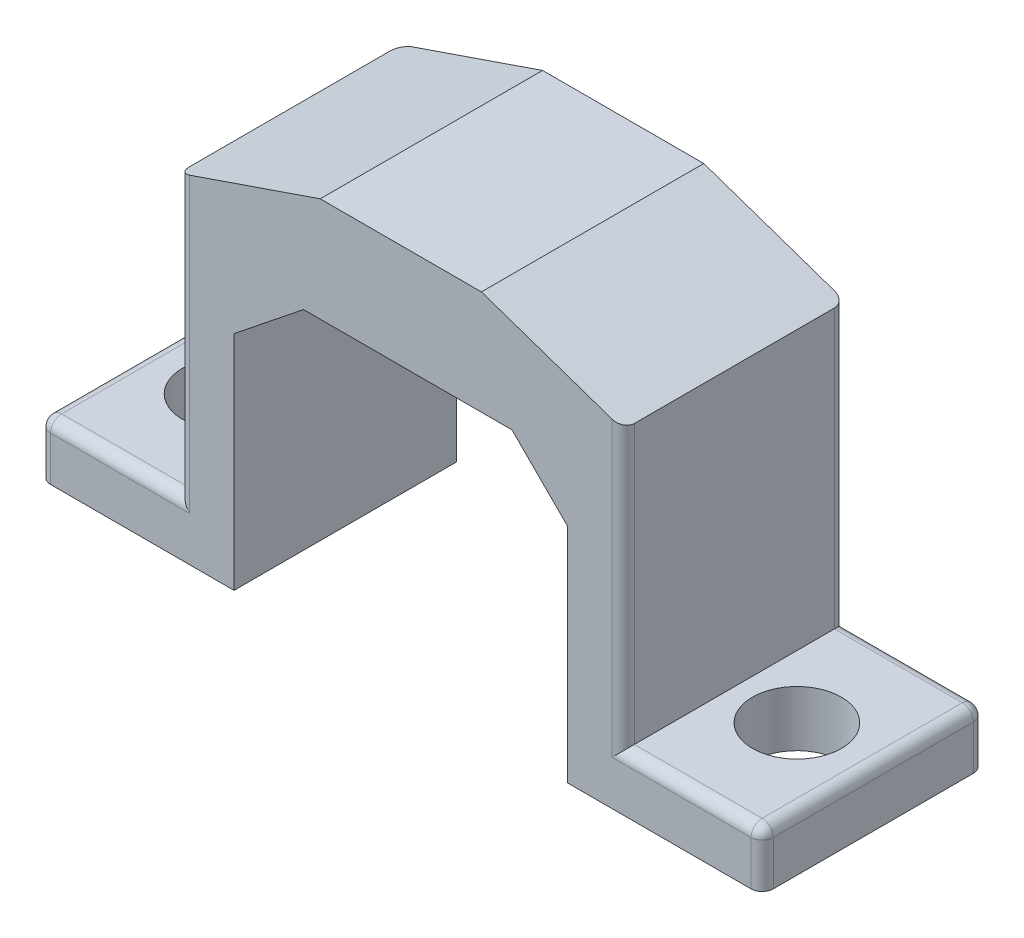
SolidWorks part; units mm, degrees
ref_plane "Ebene vorne" through (0, 0, 0) normal (0, 0, 1) x (1, 0, 0)
ref_plane "Ebene oben" through (0, 0, 0) normal (0, 1, 0) x (1, 0, 0)
ref_plane "Ebene rechts" through (0, 0, 0) normal (1, 0, 0) x (0, 0, -1)
sketch "Skizze1" plane through (0, 0, 0) normal (0, 0, 1) x (1, 0, 0)
  line L0 (0, 0) -> (7, 0)
  line L1 (7, 0) -> (7, 10)
  line L2 (7, 10) -> (19, 10)
  line L3 (19, 10) -> (19, 0)
  line L4 (19, 0) -> (26, 0)
  line L5 (26, 0) -> (26, 2)
  line L6 (26, 2) -> (21, 2)
  line L7 (21, 2) -> (21, 12)
  line L9 (5, 12) -> (5, 2)
  line L10 (5, 2) -> (0, 2)
  line L11 (0, 2) -> (0, 0)
  line L14 (15.9, 13.75) -> (21, 12)
  line L15 (5, 12) -> (10.1, 13.75)
  line L16 (10.1, 13.75) -> (15.9, 13.75)
  dimension "D1" = 12
  dimension "D2" = 10
  dimension "D3" = 7
  dimension "D4" = 7
  dimension "D5" = 5.1
  dimension "D6" = 16
  dimension "D7" = 10
  dimension "D8" = 10
  dimension "D9" = 2
  dimension "D10" = 2
  dimension "D11" = 2
  dimension "D12" = 3.75
  dimension "D13" = 5.1
extrude "Grundkörper" add sketch "Skizze1" along normal blind 8
sketch "Skizze4" plane through (0, 0, 0) normal (0, -1, 0) x (1, 0, 0)
  line L0 (26, 8) -> (26, 0) construction
  line L3 (19, 0) -> (26, 0) construction
  circle A0 centre (23.25, 4) radius 1.6
  dimension "D1" = 3.2
  dimension "D3" = 4
  dimension "D2" = 2.75
extrude "Schrauben-Bohrung" cut sketch "Skizze4" against normal blind 3
ref_plane "Ebene1" through (0, 2, 0) normal (0, -1, 0) x (-1, 0, 0)
ref_plane "Ebene2" through (13, 0, 0) normal (1, 0, 0) x (0, 0, -1)
fillet "Verrundung1" radius 0.4 13 edges at (23.5, 2, 0) (23.5, 2, 8) (2.5, 2, 0) (2.5, 2, 8) (5, 7, 8) (5, 7, 0) (21, 7, 8) (21, 7, 0) (26, 1, 0) (26, 1, 8) (26, 2, 4) (0, 2, 4) (0, 1, 8)
ref_plane "Ebene3" through (25.6, 1.6, 8) normal (-1, 0, 0) x (0, 0, 1)
sketch "Skizze8" plane through (0, 0, 8) normal (0, 0, 1) x (1, 0, 0)
  line L0 (9.5, 10) -> (7, 8)
  line L1 (7, 10) -> (19, 10) construction
  line L2 (7, 0) -> (7, 10) construction
  line L3 (7, 8) -> (7, 10)
  line L4 (7, 10) -> (9.5, 10)
  line L5 (17, 10) -> (19, 10)
  line L6 (19, 10) -> (19, 8)
  line L7 (19, 10) -> (19, 0) construction
  line L8 (19, 8) -> (17, 10)
  dimension "D1" = 2
  dimension "D2" = 2
extrude "Dreiecke_seitlich_Halter" add sketch "Skizze8" against normal blind 0.75
ref_plane "Ebene4" through (0, 0, 5) normal (0, 0, 1) x (1, 0, 0)
mirror "Spiegeln_seitlich_Halter" about plane through (0, 0, 5) normal (0, 0, 1) of "Dreiecke_seitlich_Halter"
mirror "Spiegeln5" about plane through (13, 0, 0) normal (1, 0, 0) of "Schrauben-Bohrung"
